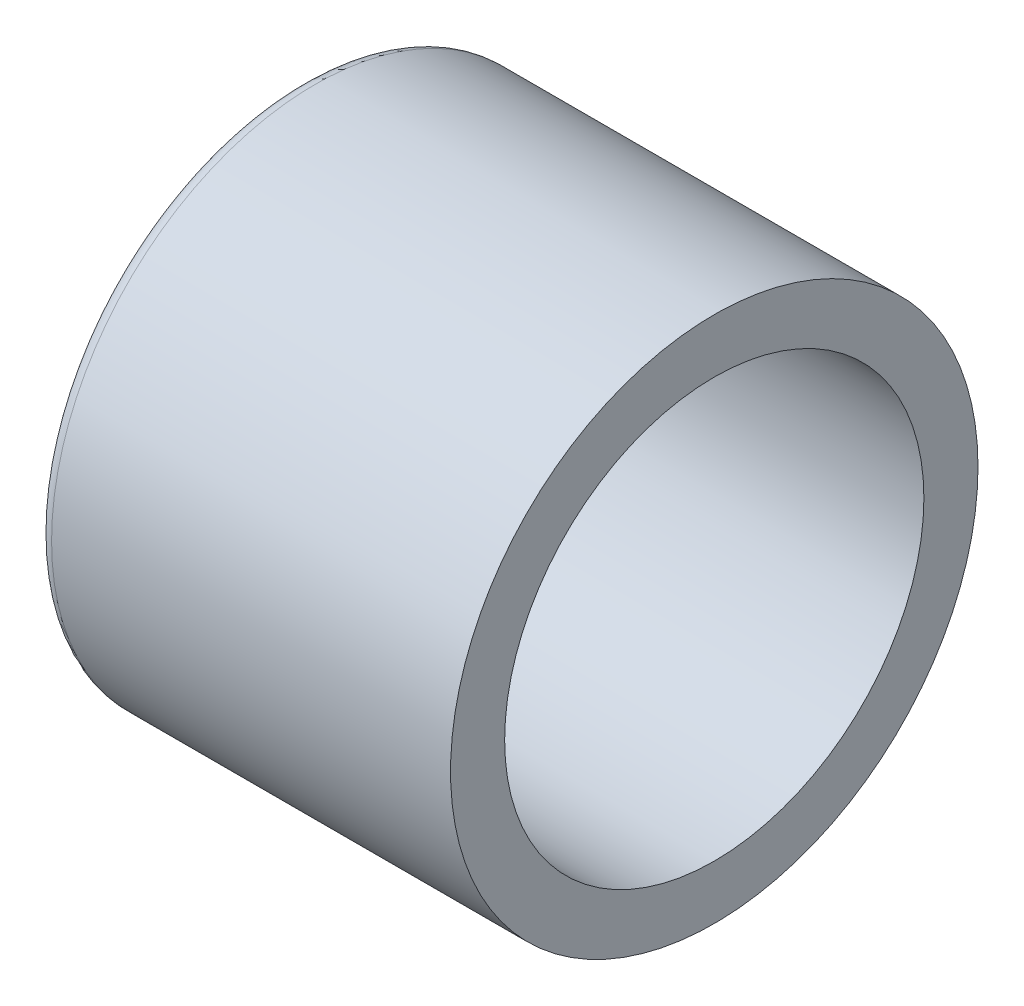
SolidWorks part; units mm, degrees
ref_plane "Front Plane" through (0, 0, 0) normal (0, 0, 1) x (1, 0, 0)
ref_plane "Top Plane" through (0, 0, 0) normal (0, 1, 0) x (1, 0, 0)
ref_plane "Right Plane" through (0, 0, 0) normal (1, 0, 0) x (0, 0, -1)
ref_axis "X-Axis" through (88.99, 0, 0) along (-1, 0, 0)
ref_axis "Y-Axis" through (0, 0, -88.99) along (0, 0, 1)
ref_axis "Z-Axis" through (0, -55, 0) along (0, 1, 0)
sketch "Sketch1" plane through (0, 0, 0) normal (0, 0, 1) x (1, 0, 0)
  line L0 (88.99, 0) -> (-88.99, 0) construction
  line L1 (-30.5, 39) -> (30.5, 39)
  line L2 (-30.5, 39) -> (-30.5, 28.5)
  line L3 (-26.5, 31) -> (30.5, 31)
  line L4 (30.5, 39) -> (30.5, 31)
  line L5 (0, -55) -> (0, 55) construction
  line L9 (-30.5, 28.5) -> (-26.5, 28.5)
  line L10 (-26.5, 31) -> (-26.5, 28.5)
  point P6 (0, 39)
  dimension "D1" = 31
  dimension "D2" = 8
  dimension "D3" = 61
  dimension "D4" = 2.5
  dimension "D5" = 4
revolve "Revolve1" add sketch "Sketch1" angle 360 about axis through (88.99, 0, 0) along (-1, 0, 0)
fillet "Fillet1" radius 2 1 edges at (-30.5, 0, -39)
chamfer "Chamfer1" distance 1 angle 45 1 edges at (-30.5, 0, -28.5)
